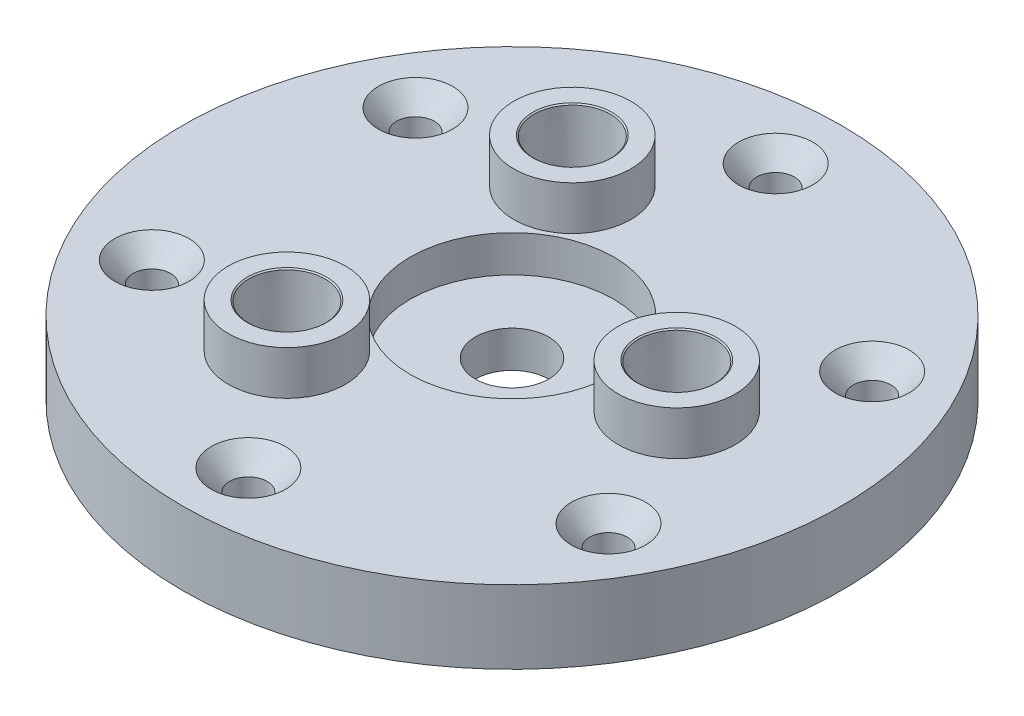
SolidWorks part; units mm, degrees
ref_plane "Front Plane" through (0, 0, 0) normal (0, 0, 1) x (1, 0, 0)
ref_plane "Top Plane" through (0, 0, 0) normal (0, 1, 0) x (1, 0, 0)
ref_plane "Right Plane" through (0, 0, 0) normal (1, 0, 0) x (0, 0, -1)
sketch "Sketch1" plane through (0, 0, 0) normal (0, 1, 0) x (1, 0, 0)
  circle A0 centre (0, 0) radius 57.15
  dimension "D1" = 114.3
extrude "Boss-Extrude1" add sketch "Sketch1" along normal blind 6.35
sketch "Sketch2" plane through (0, 6.35, 0) normal (0, 1, 0) x (1, 0, 0)
  circle A0 centre (0, 0) radius 6.35
  dimension "D1" = 12.7
extrude "Cut-Extrude1" cut sketch "Sketch2" against normal through all both and the other way through all
sketch "Sketch3" plane through (0, 6.35, 0) normal (0, 1, 0) x (1, 0, 0)
  circle A0 centre (0, 0) radius 57.15
  circle A1 centre (0, 0) radius 57.15 construction
  circle A2 centre (0, 0) radius 17.653
  dimension "D1" = 35.306
extrude "Boss-Extrude2" add sketch "Sketch3" along normal blind 6.35
sketch "Sketch4" plane through (0, 12.7, 0) normal (0, 1, 0) x (1, 0, 0)
  line L0 (0, 0) -> (57.15, 0) construction
  line L1 (0, 0) -> (-28.575, -49.4934) construction
  line L2 (0, 0) -> (-28.575, 49.4934) construction
  circle A0 centre (0, 0) radius 57.15 construction
  circle A1 centre (28.575, 0) radius 3.175
  circle A2 centre (-14.2875, -24.7467) radius 3.175
  circle A3 centre (-14.2875, 24.7467) radius 3.175
  circle A4 centre (0, 0) radius 28.575 construction
  point P9 (0, 0)
  point P17 (0, 0)
  dimension "D1" = 6.35
  dimension "D2" = 57.15
  dimension "D3" = 3
extrude "Cut-Extrude2" cut sketch "Sketch4" against normal through all both and the other way through all
hole_wizard "CSK for 1/4 Flat Head Machine Screw1" positions "3DSketch1" profile "Sketch6" countersink size "1/4" standard "ANSI Inch" end condition through all
sketch3d "3DSketch1"
  line L3 (0, 12.7, 0) -> (0, 12.7, -45.72) construction
  line L4 (0, 12.7, 0) -> (0, 6.35, 0) construction
  point P0 (0, 12.7, -45.72)
  dimension "D1" = 45.72
sketch "Sketch6" plane through (0, 12.7, -45.72) normal (1, 0, 0) x (0, 0, 1)
  line L0 (0, 0) -> (0, 12.7)
  line L1 (0, 12.7) -> (3.2639, 12.7)
  line L2 (3.2639, 12.7) -> (3.2639, 3.6524)
  line L3 (3.2639, 3.6524) -> (6.4389, 0)
  line L5 (6.4389, 0) -> (0, 0)
  line L6 (-3.2639, 3.6524) -> (-6.4389, 0) construction
  line L11 (0, -6.35) -> (0, 107.95) construction
  dimension "Thru Hole Dia." = 6.5278
  dimension "Thru Hole Depth" = 12.7
  dimension "Near C'Sink Dia." = 12.8778
  dimension "Near C'Sink Angle" = 82
sketch "Sketch8" plane through (0, 12.7, 0) normal (0, 1, 0) x (1, 0, 0)
  circle A0 centre (0, 0) radius 35.7188 construction
  circle A2 centre (0, 0) radius 38.1 construction
  dimension "D1" = 76.2
  dimension "D2" = 71.4375
pattern_circular "CirPattern1" count 6 over 360 about axis through (0, 6.35, 0) along (0, 1, 0) of "CSK for 1/4 Flat Head Machine Screw1"
sketch "Sketch11" plane through (0, 12.7, 0) normal (0, 1, 0) x (1, 0, 0)
  circle A0 centre (-14.2875, 24.7467) radius 3.175
  circle A1 centre (28.575, 0) radius 3.175
  circle A2 centre (-14.2875, -24.7467) radius 3.175
  circle A4 centre (-14.2875, 24.7467) radius 3.175 construction
  circle A5 centre (28.575, 0) radius 3.175 construction
  circle A6 centre (-14.2875, -24.7467) radius 3.175 construction
  circle A7 centre (-14.2875, 24.7467) radius 10.16
  circle A8 centre (28.575, 0) radius 10.16
  circle A9 centre (-14.2875, -24.7467) radius 10.16
  dimension "D1" = 20.32
extrude "Boss-Extrude3" add sketch "Sketch11" along normal blind 7.62
hole_wizard "1/4 NPT Tapped Hole3" positions "Sketch12" profile "Sketch13" size "1/4" standard "ANSI Inch"
sketch "Sketch12" plane through (0, 20.32, 0) normal (0, 1, 0) x (1, 0, 0)
  point P0 (-14.2875, 24.7467)
  point P3 (28.575, 0)
  point P6 (-14.2875, -24.7467)
sketch "Sketch13" plane through (-14.2875, 20.32, -24.7467) normal (1, 0, 0) x (0, 0, 1)
  line L0 (0, 0) -> (0, 20.4111)
  line L1 (5.5626, 17.0688) -> (0, 20.4111)
  line L2 (-5.5626, 17.0688) -> (0, 20.4111) construction
  line L3 (5.5626, 17.0688) -> (5.5626, 10.0203)
  line L4 (5.5626, 10.0203) -> (6.3356, 10.0203)
  line L5 (6.3356, 10.0203) -> (6.6298, 0.1914)
  line L6 (6.6298, 0.1914) -> (6.858, 0)
  line L7 (6.858, 0) -> (0, 0)
  line L8 (0, -6.35) -> (0, 107.95) construction
  line L9 (-6.6298, 0.1914) -> (-6.858, 0) construction
  line L11 (-5.5626, 10.0203) -> (-6.3356, 10.0203) construction
  line L12 (-6.3356, 10.0203) -> (-6.6298, 0.1914) construction
  dimension "Tap Drill Dia." = 11.1252
  dimension "Tap Drill Depth" = 17.0688
  dimension "Thread Dia." = 13.2597
  dimension "Thread Angle" = 3.43
  dimension "Thread Depth" = 10.0203
  dimension "C'Sink Dia." = 13.716
  dimension "C'Sink Angle" = 100
  dimension "Drill Angle" = 118
